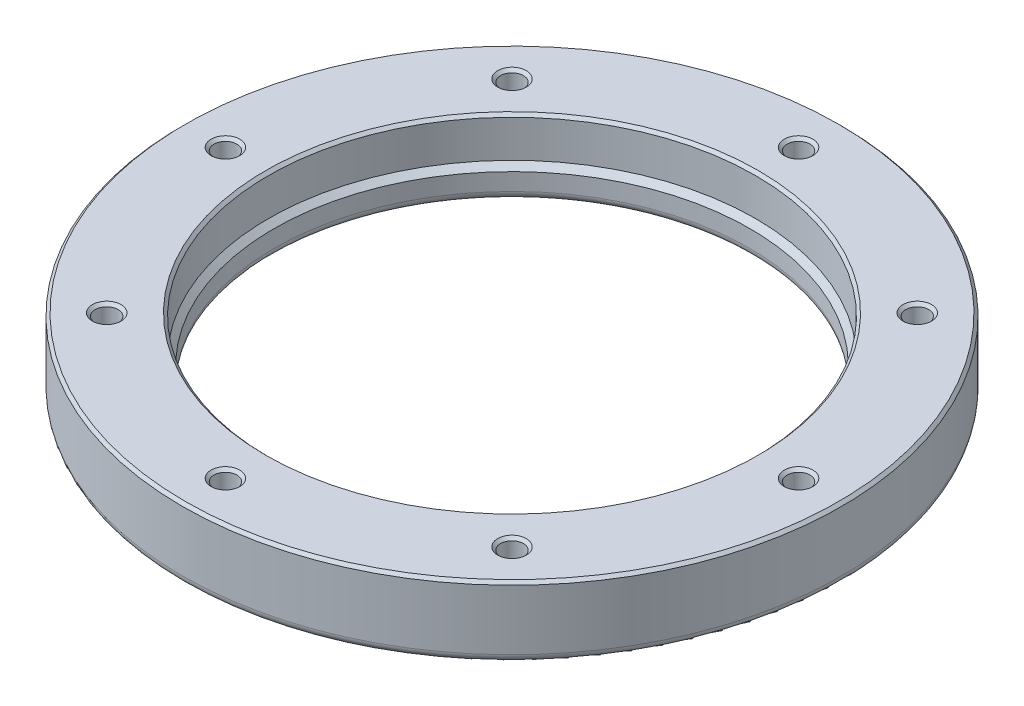
SolidWorks part; units mm, degrees
ref_plane "Front Plane" through (0, 0, 0) normal (0, 0, 1) x (1, 0, 0)
ref_plane "Top Plane" through (0, 0, 0) normal (0, 1, 0) x (1, 0, 0)
ref_plane "Right Plane" through (0, 0, 0) normal (1, 0, 0) x (0, 0, -1)
sketch "Sketch2" plane through (0, 0, 0) normal (0, 1, 0) x (1, 0, 0)
  circle A0 centre (0, 0) radius 115
  dimension "D1" = 230
extrude "Boss-Extrude1" add sketch "Sketch2" along normal blind 25
sketch "Sketch3" plane through (0, 25, 0) normal (0, 1, 0) x (1, 0, 0)
  circle A0 centre (0, 0) radius 85
  dimension "D1" = 170
extrude "Cut-Extrude1" cut sketch "Sketch3" against normal blind 16
sketch "Sketch4" plane through (0, 9, 0) normal (0, 1, 0) x (1, 0, 0)
  circle A0 centre (0, 0) radius 83
  dimension "D1" = 166
extrude "Cut-Extrude2" cut sketch "Sketch4" against normal through all
chamfer "Chamfer3" distance 2 angle 45 1 edges at (0, 9, 85)
chamfer "Chamfer5" distance 1 angle 45 2 edges at (0, 25, 85) (0, 25, 115)
fillet "Fillet1" radius 3 2 edges at (0, 0, 83) (0, 0, 115)
sketch "Sketch5" plane through (0, 25, 0) normal (0, 1, 0) x (1, 0, 0)
  line L0 (0, 0) -> (-169.6567, 0) construction
  circle A0 centre (-100, 0) radius 4
  circle A1 centre (-70.7107, 70.7107) radius 4
  circle A2 centre (0, 100) radius 4
  circle A3 centre (70.7107, 70.7107) radius 4
  circle A4 centre (100, 0) radius 4
  circle A5 centre (70.7107, -70.7107) radius 4
  circle A6 centre (0, -100) radius 4
  circle A7 centre (-70.7107, -70.7107) radius 4
  point P21 (0, 0)
  dimension "D1" = 100
  dimension "D2" = 8
  dimension "D3" = 8
extrude "Cut-Extrude3" cut sketch "Sketch5" against normal blind 15
sketch "Sketch6" plane through (0, 0, 0) normal (0, -1, 0) x (1, 0, 0)
  line L0 (0, 0) -> (-154.1822, 0) construction
  circle A0 centre (-100, 0) radius 6
  circle A1 centre (-70.7107, 70.7107) radius 6
  circle A2 centre (0, 100) radius 6
  circle A3 centre (70.7107, 70.7107) radius 6
  circle A4 centre (100, 0) radius 6
  circle A5 centre (70.7107, -70.7107) radius 6
  circle A6 centre (0, -100) radius 6
  circle A7 centre (-70.7107, -70.7107) radius 6
  point P22 (0, 0)
  dimension "D1" = 100
  dimension "D2" = 12
  dimension "D3" = 8
extrude "Cut-Extrude4" cut sketch "Sketch6" against normal blind 10
chamfer "Chamfer6" distance 1 angle 45 8 edges at (70.7107, 25, -66.7107) (100, 25, 4) (70.7107, 25, 74.7107) (0, 25, 104) (-70.7107, 25, 74.7107) (-100, 25, 4) (0, 25, -96) (-70.7107, 25, -66.7107)
